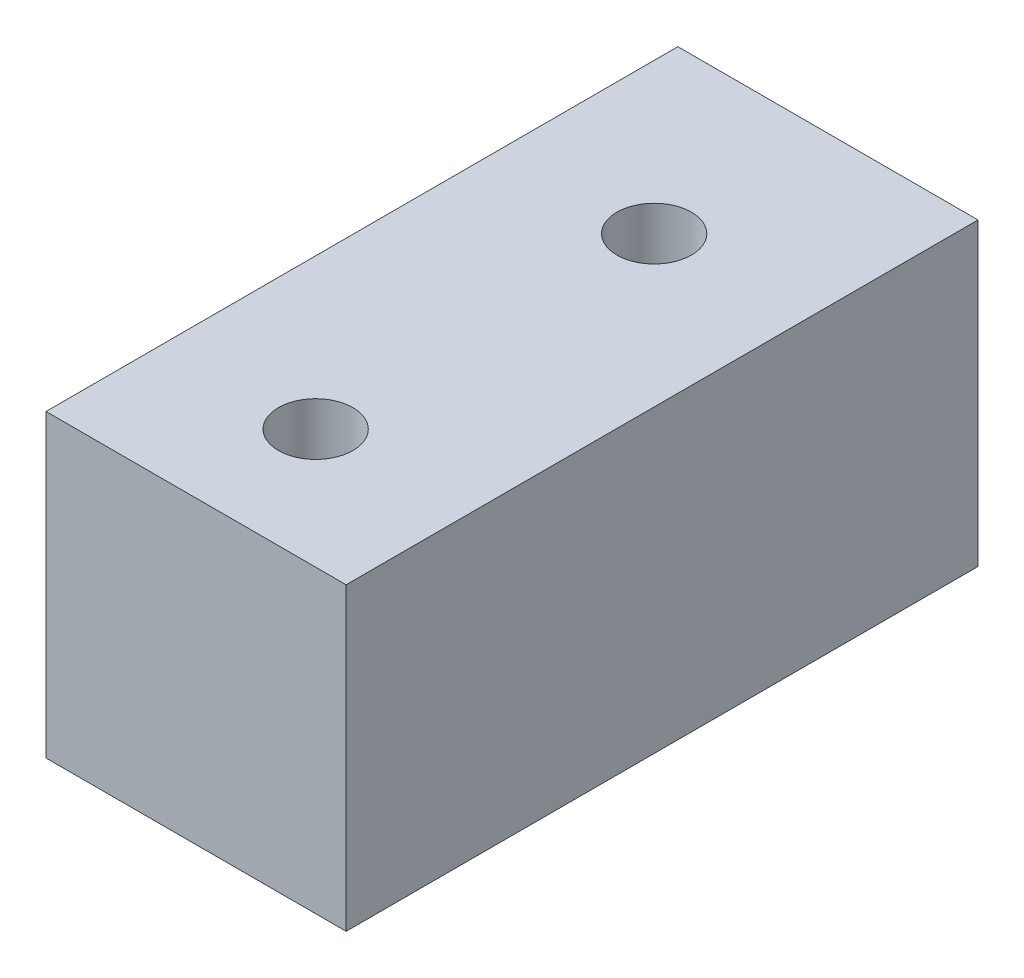
SolidWorks part; units mm, degrees
ref_plane "Спереди" through (0, 0, 0) normal (0, 0, 1) x (1, 0, 0)
ref_plane "Сверху" through (0, 0, 0) normal (0, 1, 0) x (1, 0, 0)
ref_plane "Справа" through (0, 0, 0) normal (1, 0, 0) x (0, 0, -1)
sketch "Эскиз1" plane through (0, 0, 0) normal (0, 0, 1) x (1, 0, 0)
  line L1 (-6.65, 6.65) -> (6.65, 6.65)
  line L2 (-6.65, 6.65) -> (-6.65, -6.65)
  line L3 (-6.65, -6.65) -> (6.65, -6.65)
  line L4 (6.65, 6.65) -> (6.65, -6.65)
  line L5 (-6.65, 6.65) -> (6.65, -6.65) construction
  line L6 (-6.65, -6.65) -> (6.65, 6.65) construction
  point P0 (0, 0)
  dimension "D1" = 13.3
extrude "Бобышка-Вытянуть1" add sketch "Эскиз1" along normal blind 28
sketch "Эскиз2" plane through (0, 6.65, 0) normal (0, 1, 0) x (1, 0, 0)
  line L0 (0, 0) -> (0, -28) construction
  line L1 (6.65, -28) -> (-6.65, -28) construction
  line L2 (6.65, 0) -> (-6.65, 0) construction
  circle A0 centre (0, -7.7) radius 1.65
  circle A1 centre (0, -22.7) radius 1.65
  dimension "D1" = 3.3
  dimension "D2" = 7.7
  dimension "D3" = 15
extrude "Вырез-Вытянуть1" cut sketch "Эскиз2" against normal through all
